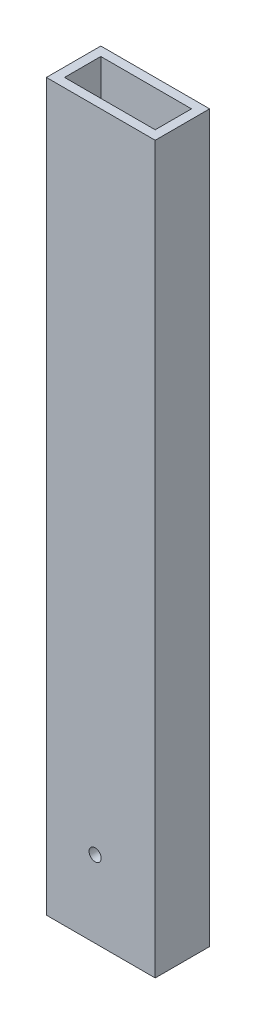
SolidWorks part; units mm, degrees
ref_plane "Front Plane" through (0, 0, 0) normal (0, 0, 1) x (1, 0, 0)
ref_plane "Top Plane" through (0, 0, 0) normal (0, 1, 0) x (1, 0, 0)
ref_plane "Right Plane" through (0, 0, 0) normal (1, 0, 0) x (0, 0, -1)
sketch "Sketch1" plane through (0, 0, 0) normal (0, 1, 0) x (1, 0, 0)
  line L0 (3.175, 15.875) -> (34.925, 15.875)
  line L1 (0, 0) -> (38.1, 0)
  line L2 (0, 0) -> (0, 19.05)
  line L3 (0, 19.05) -> (38.1, 19.05)
  line L4 (38.1, 0) -> (38.1, 19.05)
  line L5 (34.925, 3.175) -> (34.925, 15.875)
  line L6 (3.175, 3.175) -> (34.925, 3.175)
  line L7 (3.175, 3.175) -> (3.175, 15.875)
  dimension "D1" = 38.1
  dimension "D2" = 19.05
extrude "Boss-Extrude1" add sketch "Sketch1" along normal blind 254
sketch "Sketch2" plane through (0, 0, -19.05) normal (0, 0, -1) x (-1, 0, 0)
  circle A1 centre (-17.0622, 26.8327) radius 2.125
extrude "Cut-Extrude1" cut sketch "Sketch2" against normal through all
